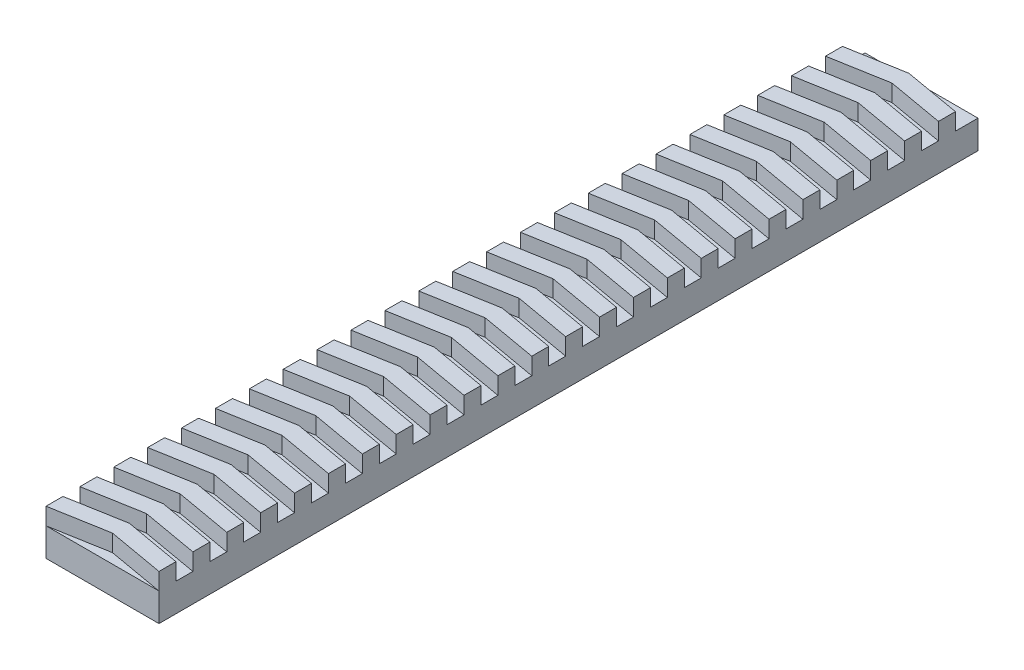
SolidWorks part; units mm, degrees
ref_plane "Front Plane" through (0, 0, 0) normal (0, 0, 1) x (1, 0, 0)
ref_plane "Top Plane" through (0, 0, 0) normal (0, 1, 0) x (1, 0, 0)
ref_plane "Right Plane" through (0, 0, 0) normal (1, 0, 0) x (0, 0, -1)
sketch "Sketch2" plane through (0, 0, 0) normal (0, 1, 0) x (1, 0, 0)
  line L1 (-10, -72.5) -> (10, -72.5)
  line L2 (-10, -72.5) -> (-10, 72.5)
  line L3 (-10, 72.5) -> (10, 72.5)
  line L4 (10, -72.5) -> (10, 72.5)
  line L5 (-10, -72.5) -> (10, 72.5) construction
  line L6 (-10, 72.5) -> (10, -72.5) construction
  point P0 (0, 0)
  dimension "D1" = 145
  dimension "D2" = 20
extrude "Boss-Extrude1" add sketch "Sketch2" along normal blind 5
sketch "Sketch3" plane through (0, 5, 0) normal (0, 1, 0) x (1, 0, 0)
  line L0 (0, -72.5) -> (0, 72.5) construction
  line L1 (-10, -72.5) -> (10, -72.5) construction
  line L2 (10, 72.5) -> (-10, 72.5) construction
  line L3 (-10, -72.5) -> (0, -70.7367)
  line L4 (0, -70.7367) -> (10, -72.5)
  line L5 (0, -67.7367) -> (-10, -69.5)
  line L6 (-10, 72.5) -> (-10, -72.5) construction
  line L7 (0, -67.7367) -> (10, -69.5)
  line L8 (10, -72.5) -> (10, 72.5) construction
  line L9 (-10, -69.5) -> (-10, -72.5)
  line L10 (10, -69.5) -> (10, -72.5)
  point P9 (0, -67.7367)
  dimension "D1" = 10
  dimension "D2" = 3
extrude "Boss-Extrude2" add sketch "Sketch3" along normal blind 3
sketch "Sketch4" plane through (-10, 0, 0) normal (-1, 0, 0) x (0, 0, 1)
  line L0 (69.5, 8) -> (72.5, 8) construction
  line L1 (69.5, 8) -> (69.5, 5) construction
  line L2 (72.5, 8) -> (72.5, 5) construction
  line L3 (69.5, 6.5) -> (72.5, 6.5) construction
  line L4 (71, 8) -> (71, 4.9346) construction
  line L5 (70.25, 8) -> (69.5, 8)
  line L6 (69.5, 8) -> (69.5, 5)
  line L7 (71.75, 8) -> (72.5, 8)
  line L8 (72.5, 8) -> (72.5, 5)
  spline S0 degree 2 poles (70.25, 8) (69.4504, 6.6039) (69.5, 5) knots 0 0 0 1 1 1
  spline S1 degree 2 poles (71.75, 8) (72.5496, 6.6039) (72.5, 5) knots 0 0 0 1 1 1
  point P0 (70.25, 8)
  point P10 (69.65, 6.5)
  dimension "D1" = 0.75
  dimension "D3" = 0.15
pattern_linear "LPattern1" count 24 spacing 6 along (0, 0, -1) of "Boss-Extrude2"
